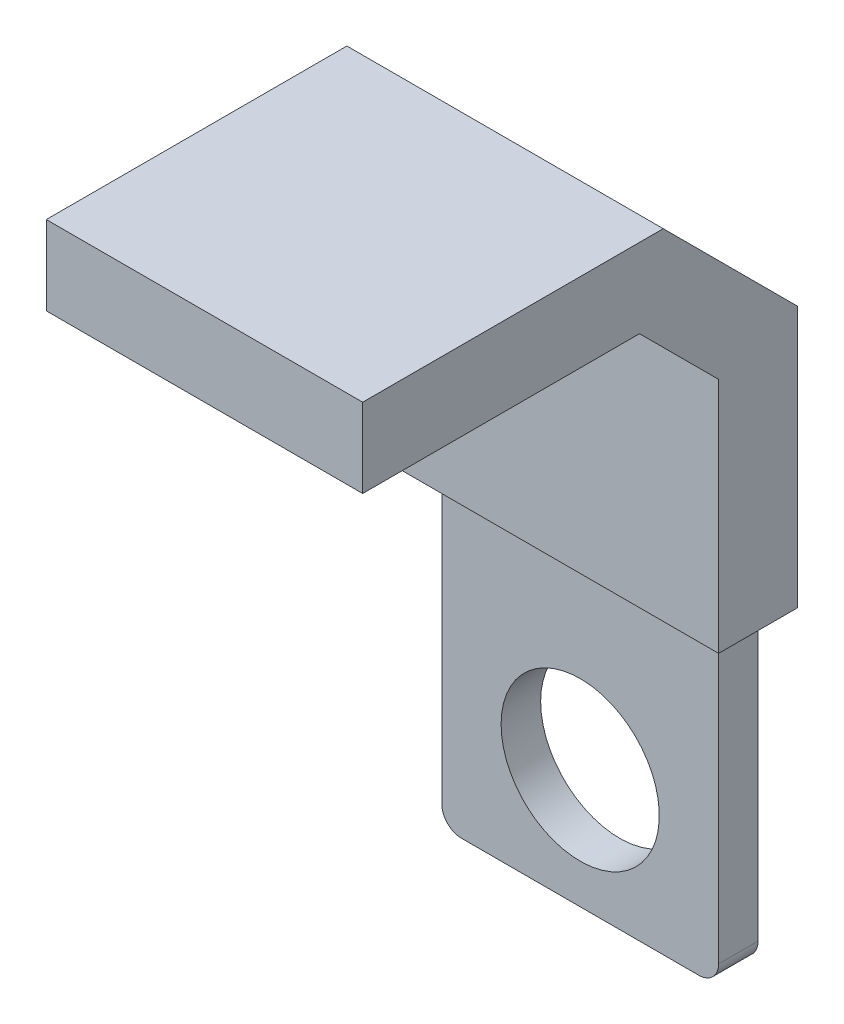
SolidWorks part; units mm, degrees
material "Czyste srebro"
ref_plane "Front Plane" through (0, 0, 0) normal (0, 0, 1) x (1, 0, 0)
ref_plane "Top Plane" through (0, 0, 0) normal (0, 1, 0) x (1, 0, 0)
ref_plane "Right Plane" through (0, 0, 0) normal (1, 0, 0) x (0, 0, -1)
sketch "Szkic1" plane through (0, 0, 0) normal (0, 1, 0) x (1, 0, 0)
  line L1 (-2, -0.5) -> (2, -0.5)
  line L2 (-2, -0.5) -> (-2, 0.5)
  line L3 (-2, 0.5) -> (2, 0.5)
  line L4 (2, -0.5) -> (2, 0.5)
  line L5 (-2, -0.5) -> (2, 0.5) construction
  line L6 (-2, 0.5) -> (2, -0.5) construction
  point P0 (0, 0)
  dimension "D1" = 4
  dimension "D2" = 1
extrude "Dodanie-wyciągnięcie5" add sketch "Szkic1" along normal blind 5 contours L3 L4 L1 L2
sketch "Szkic6" plane through (0, 0, 0.5) normal (0, 0, 1) x (1, 0, 0)
  line L0 (-2, 5) -> (-2, 0) construction
  line L1 (2, 5) -> (-2, 5)
  line L2 (2, 5) -> (2, 4)
  line L3 (2, 4) -> (-2, 4)
  line L4 (-2, 5) -> (-2, 4)
extrude "Dodanie-wyciągnięcie6" add sketch "Szkic6" along normal blind 4.5
chamfer "Sfazowanie2" distance 1 angle 45 1 edges at (0, 4, 0.5)
chamfer "Sfazowanie4" distance 1.7 angle 45 1 edges at (0, 5, -0.5)
sketch "Szkic13" plane through (0, 0, 0) normal (0, -1, 0) x (1, 0, 0)
  line L1 (1.75, -0.25) -> (-1.75, -0.25)
  line L2 (1.75, -0.25) -> (1.75, 0.25)
  line L3 (1.75, 0.25) -> (-1.75, 0.25)
  line L4 (-1.75, -0.25) -> (-1.75, 0.25)
  line L5 (1.75, -0.25) -> (-1.75, 0.25) construction
  line L6 (1.75, 0.25) -> (-1.75, -0.25) construction
  point P0 (0, 0)
extrude "Dodanie-wyciągnięcie7" add sketch "Szkic13" along normal blind 3.9
fillet "Zaokrąglenie1" radius 0.25 4 edges at (1.75, 0, 0) (0, 0, -0.25) (-1.75, 0, 0) (0, 0, 0.25)
sketch "Szkic14" plane through (0, 0, -0.25) normal (0, 0, -1) x (-1, 0, 0)
  line L0 (0, -3.9) -> (0, -2.4008) construction
  line L1 (1.75, -3.9) -> (-1.75, -3.9) construction
  circle A0 centre (0, -2.4008) radius 1
extrude "Wytnij-wyciągnięcie1" cut sketch "Szkic14" against normal blind 3.9
fillet "Zaokrąglenie2" radius 0.25 2 edges at (-1.75, -3.9, 0) (1.75, -3.9, 0)
